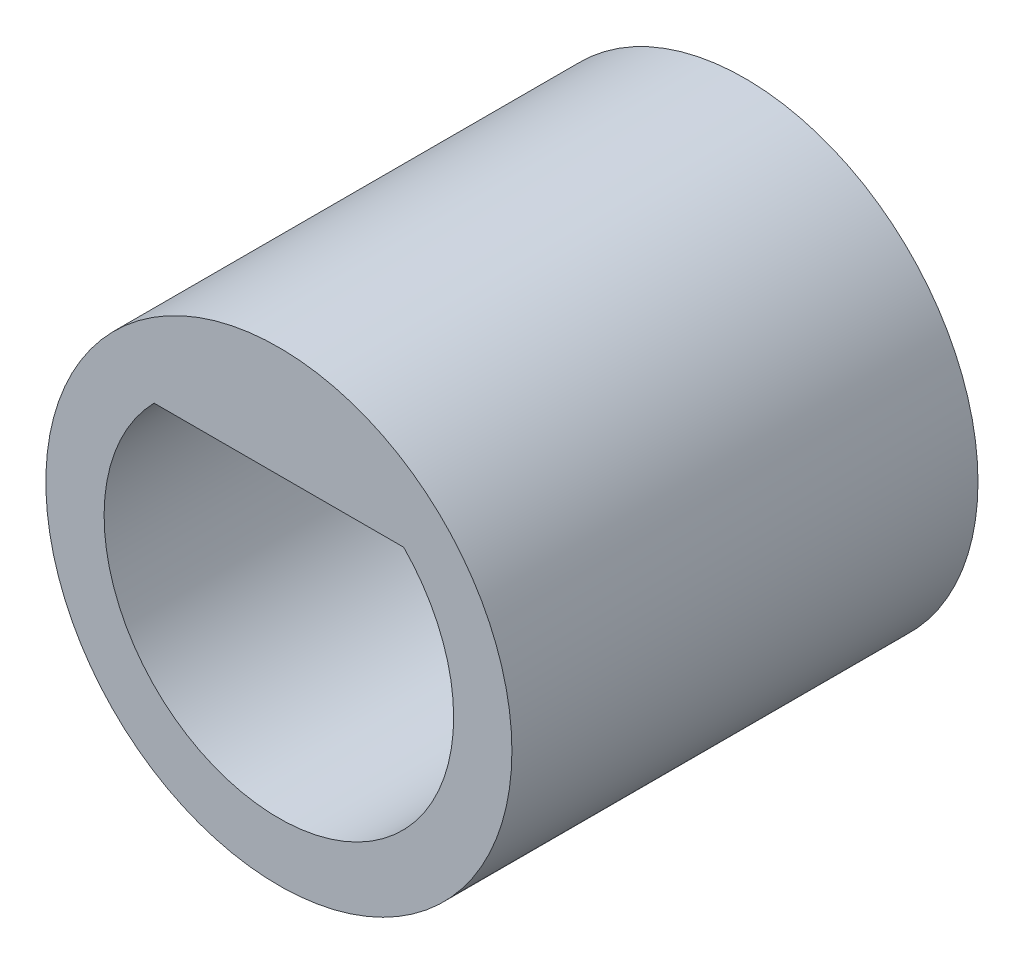
SolidWorks part; units mm, degrees
ref_plane "Plan de face" through (0, 0, 0) normal (0, 0, 1) x (1, 0, 0)
ref_plane "Plan de dessus" through (0, 0, 0) normal (0, 1, 0) x (1, 0, 0)
ref_plane "Plan de droite" through (0, 0, 0) normal (1, 0, 0) x (0, 0, -1)
sketch "Esquisse1" plane through (0, 0, 0) normal (0, 0, 1) x (1, 0, 0)
  line L0 (-2.1424, 2.1) -> (2.1424, 2.1)
  line L1 (-0.9885, -3) -> (1.037, -3) construction
  circle A0 centre (0, 0) radius 4
  arc A1 (-2.1424, 2.1) -> (2.1424, 2.1) centre (0, 0) ccw
  dimension "D1" = 8
  dimension "D2" = 6
  dimension "D3" = 5.1
extrude "Boss.-Extru.1" add sketch "Esquisse1" along normal blind 8
